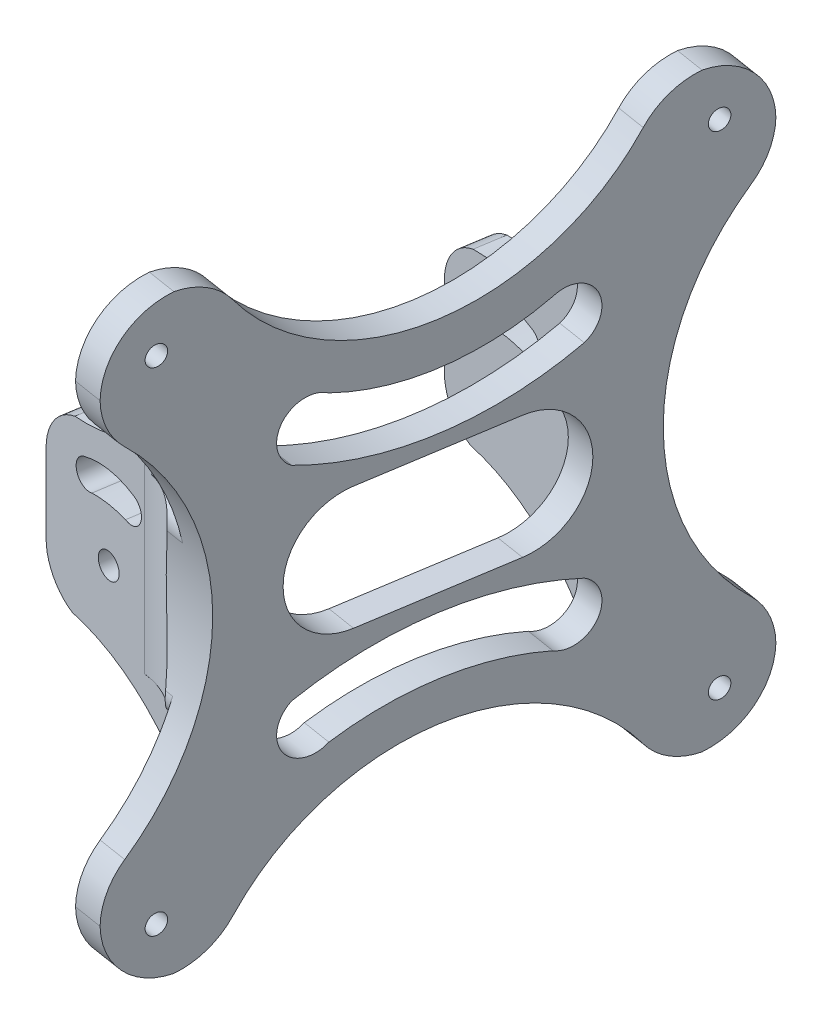
SolidWorks part; units mm, degrees
ref_plane "Plan de face" through (0, 0, 0) normal (0, 0, 1) x (1, 0, 0)
ref_plane "Plan de dessus" through (0, 0, 0) normal (0, 1, 0) x (1, 0, 0)
ref_plane "Plan de droite" through (0, 0, 0) normal (1, 0, 0) x (0, 0, -1)
sketch "Esquisse2" plane through (0.9062, 0, -5.7217) normal (-0.1564, 0, 0.9877) x (0.9877, 0, 0.1564)
  line L0 (50, 13.8449) -> (13, 13.8449)
  line L1 (13, 13.8449) -> (13, -22.1551)
  line L6 (13, -22.1551) -> (50, -22.1551)
  line L7 (50, 13.8449) -> (50, -22.1551)
  circle A0 centre (28.3, -8.1551) radius 2.55
  arc A9 (34.496, 7.5776) -> (32.4193, 2.2798) centre (33.4577, 4.9287) cw
  arc A11 (22.1493, 7.5776) -> (24.2261, 2.2798) centre (23.1877, 4.9287) ccw
  arc A12 (22.1493, 7.5776) -> (34.496, 7.5776) centre (28.3227, -8.1708) cw
  arc A14 (24.2261, 2.2798) -> (32.4193, 2.2798) centre (28.3227, -21.4961) cw
  dimension "D1" = 36
  dimension "D2" = 37
  dimension "D3" = 15.3
  dimension "D4" = 14
extrude "Boss.-Extru.1" add sketch "Esquisse2" along normal blind 6
sketch "Esquisse8" plane through (11.0275, 0, -69.6251) normal (0.1564, 0, -0.9877) x (-0.9877, 0, -0.1564)
  line L0 (-50, 13.8449) -> (-13, 13.8449)
  line L5 (-13, 13.8449) -> (-13, -22.1551)
  line L6 (-13, -22.1551) -> (-50, -22.1551)
  line L7 (-50, -22.1551) -> (-50, 13.8449)
  circle A0 centre (-28.3, -8.1551) radius 2.55
  arc A1 (-22.1493, 7.5776) -> (-24.2261, 2.2798) centre (-23.1877, 4.9287) cw
  arc A2 (-34.496, 7.5776) -> (-32.4193, 2.2798) centre (-33.4577, 4.9287) ccw
  arc A3 (-34.496, 7.5776) -> (-22.1493, 7.5776) centre (-28.3227, -8.1708) cw
  arc A5 (-32.4193, 2.2798) -> (-24.2261, 2.2798) centre (-28.3227, -20.7951) cw
  point P14 (-28.6739, -22.1551)
  dimension "D1" = 15.3
  dimension "D2" = 14
  dimension "D3" = 36
extrude "Boss.-Extru.3" add sketch "Esquisse8" along normal blind 6 separate body
sketch "Esquisse7" plane through (49.3844, 0, 7.8217) normal (0.9877, 0, 0.1564) x (0.1564, 0, -0.9877)
  line L6 (-21.8658, 59.4655) -> (98.1342, 59.4655)
  line L7 (-21.8658, 59.4655) -> (-21.8658, -60.5345)
  line L8 (-21.8658, -60.5345) -> (98.1342, -60.5345)
  line L9 (98.1342, 59.4655) -> (98.1342, -60.5345)
  circle A0 centre (-11.8658, 49.4655) radius 2
  circle A1 centre (88.1342, 49.4655) radius 2
  circle A2 centre (88.1342, -50.5345) radius 2
  circle A3 centre (-11.8658, -50.5345) radius 2
extrude "Boss.-Extru.5" add sketch "Esquisse7" along normal blind 6
sketch "Esquisse13" plane through (49.3844, 0, 7.8217) normal (-0.9877, 0, -0.1564) x (-0.1564, 0, 0.9877)
  line L0 (-98.1342, -60.5345) -> (-98.1342, 59.4655) construction
  line L1 (-76.493, 13.8449) -> (-98.1342, 13.8449)
  line L2 (-76.493, 13.8449) -> (-76.493, -22.048)
  line L3 (-76.493, -22.048) -> (-98.1342, -22.048)
  line L4 (-98.1342, 13.8449) -> (-98.1342, -22.048)
  line L5 (21.8658, 59.4655) -> (21.8658, -60.5345) construction
  line L6 (0.207, 13.8449) -> (21.8658, 13.8449)
  line L7 (0.207, 13.8449) -> (0.207, -22.2148)
  line L8 (0.207, -22.2148) -> (21.8658, -22.2148)
  line L9 (21.8658, 13.8449) -> (21.8658, -22.2148)
extrude "Boss.-Extru.6" add sketch "Esquisse13" along normal blind 13
sketch "Esquisse9" plane through (49.3844, 0, 7.8217) normal (-0.9877, 0, -0.1564) x (-0.1564, 0, 0.9877)
  line L0 (-98.1342, -60.5345) -> (-98.1342, -22.048) construction
  line L1 (-98.1342, 59.4655) -> (21.8658, 59.4655) construction
  line L2 (21.8658, -60.5345) -> (-98.1342, -60.5345) construction
  line L4 (21.8658, 59.4655) -> (21.8658, 13.8449) construction
  line L5 (-98.1342, 39.4655) -> (-98.1342, -40.5345)
  line L6 (-78.1342, -60.5345) -> (1.8658, -60.5345)
  line L7 (21.8658, 39.4655) -> (21.8658, -40.5345)
  line L8 (1.8658, 59.4655) -> (-78.1342, 59.4655)
  arc A0 (-98.1342, 39.4655) -> (-98.1342, -40.5345) centre (-128.1342, -0.5345) cw
  arc A1 (-78.1342, 59.4655) -> (1.8658, 59.4655) centre (-38.1342, 80.081) ccw
  arc A2 (21.8658, 39.4655) -> (21.8658, -40.5345) centre (51.8658, -0.5345) ccw
  arc A3 (1.8658, -60.5345) -> (-78.1342, -60.5345) centre (-38.1342, -81.15) ccw
  dimension "D3" = 50
  dimension "D6" = 45
  dimension "D9" = 50
  dimension "D12" = 45
  dimension "D1" = 20
  dimension "D2" = 20
  dimension "D4" = 20
  dimension "D5" = 20
  dimension "D7" = 20
  dimension "D8" = 20
  dimension "D10" = 20
  dimension "D11" = 20
extrude "Enlèv. mat.-Extru.1" cut sketch "Esquisse9" against normal blind 10 and the other way blind 13
sketch "Esquisse10" plane through (49.3844, 0, 7.8217) normal (-0.9877, 0, -0.1564) x (-0.1564, 0, 0.9877)
  line L0 (-53.1342, -0.5345) -> (-23.1342, -0.5345) construction
  line L1 (-53.1342, 11.9655) -> (-23.1342, 11.9655)
  line L2 (-53.1342, -13.0345) -> (-23.1342, -13.0345)
  line L3 (-98.1342, 59.4655) -> (-78.1342, 59.4655) construction
  line L5 (-98.1342, 39.4655) -> (-98.1342, 59.4655) construction
  line L6 (21.8658, 59.4655) -> (21.8658, 39.4655) construction
  arc A0 (-53.1342, 11.9655) -> (-53.1342, -13.0345) centre (-53.1342, -0.5345) ccw
  arc A1 (-23.1342, -13.0345) -> (-23.1342, 11.9655) centre (-23.1342, -0.5345) ccw
  point P2 (-38.1342, -0.5345)
  dimension "D4" = 12.5
  dimension "D1" = 60
  dimension "D2" = 45
  dimension "D3" = 45
extrude "Enlèv. mat.-Extru.2" cut sketch "Esquisse10" against normal blind 10
fillet "Congé1" radius 14 12 edges at (64.5704, 59.4655, -68.8812) (67.6991, 59.4655, -88.635) (67.6991, -40.5345, -88.635) (52.0556, 59.4655, 10.1339) (48.9269, 59.4655, 29.8876) (48.9269, -40.5345, 29.8876) (67.6991, -60.5345, -88.635) (52.0556, -60.5345, 10.1339) (48.9269, 39.4655, 29.8876) (67.6991, 39.4655, -88.635) (64.5704, -60.5345, -68.8812) (48.9269, -60.5345, 29.8876)
fillet "Congé2" radius 10 4 edges at (24.3368, 13.8449, -70.5545) (24.3368, -22.1551, -70.5545) (13.2769, -22.1551, -0.725) (13.2769, 13.8449, -0.725)
sketch "Esquisse16" plane through (49.3844, 0, 7.8217) normal (-0.9877, 0, -0.1564) x (-0.1564, 0, 0.9877)
  line L0 (0.207, -22.1551) -> (-5.793, -22.1551) construction
  line L1 (-70.493, -22.1551) -> (-76.493, -22.1551)
  line L2 (-70.493, -22.1551) -> (-70.493, -41.1551)
  line L3 (-70.493, -41.1551) -> (-76.493, -41.1551)
  line L4 (-76.493, -22.1551) -> (-76.493, -41.1551)
  line L5 (-70.493, 13.8449) -> (-76.493, 13.8449)
  line L6 (-70.493, 13.8449) -> (-70.493, 33.8449)
  line L7 (-70.493, 33.8449) -> (-76.493, 33.8449)
  line L8 (-76.493, 13.8449) -> (-76.493, 33.8449)
  line L9 (-5.793, 13.8449) -> (0.207, 13.8449)
  line L10 (-5.793, 13.8449) -> (-5.793, 33.8449)
  line L11 (-5.793, 33.8449) -> (0.207, 33.8449)
  line L12 (0.207, 13.8449) -> (0.207, 33.8449)
  line L13 (-5.793, -22.1551) -> (0.207, -22.1551)
  line L14 (-5.793, -22.1551) -> (-5.793, -42.1551)
  line L15 (-5.793, -42.1551) -> (0.207, -42.1551)
  line L16 (0.207, -22.1551) -> (0.207, -42.1551)
  line L17 (-76.493, -22.1551) -> (-70.493, -22.1551) construction
  point P20 (0, 0)
  dimension "D1" = 20
  dimension "D2" = 20
  dimension "D3" = 20
  dimension "D4" = 19
  dimension "D5" = 6
  dimension "D6" = 6
  dimension "D7" = 6
  dimension "D8" = 6
  dimension "D9" = 0
  dimension "D10" = 0
extrude "Boss.-Extru.7" add sketch "Esquisse16" along normal blind 37
sketch "Esquisse17" plane through (-0.0324, 0, 0.2045) normal (-0.1564, 0, 0.9877) x (0.9877, 0, 0.1564)
  line L0 (50, 33.8449) -> (13, 33.8449)
  line L1 (13, 33.8449) -> (13, 13.5011)
  line L4 (13, -42.1551) -> (50, -42.1551) construction
  line L5 (50, -42.1551) -> (50, -22.2148) construction
  line L6 (13, -42.1551) -> (13, -21.5483)
  line L7 (13, -42.1551) -> (50, -42.1551)
  line L8 (13, 3.8449) -> (13, -12.1551) construction
  arc A2 (13, -21.5483) -> (50, -42.1551) centre (16.5937, -58.6163) cw
  arc A3 (13, 13.5011) -> (50, 33.8449) centre (17.0381, 49.9753) ccw
  point P4 (13, -21.5483)
  point P14 (13, 13.5011)
extrude "Enlèv. mat.-Extru.5" cut sketch "Esquisse17" against normal blind 102
sketch "Esquisse11" plane through (49.3844, 0, 7.8217) normal (-0.9877, 0, -0.1564) x (-0.1564, 0, 0.9877)
  circle A0 centre (-88.1342, 49.4655) radius 3.6
  circle A1 centre (11.8658, 49.4655) radius 3.6
  circle A2 centre (11.8658, -50.5345) radius 3.6
  circle A3 centre (-88.1342, -50.5345) radius 3.6
  dimension "D1" = 7.2
  dimension "D2" = 7.2
  dimension "D3" = 7.2
  dimension "D4" = 7.2
extrude "Enlèv. mat.-Extru.3" cut sketch "Esquisse11" against normal blind 2
fillet "Congé3" radius 4 4 edges at (42.3421, 13.8449, 10.734) (41.899, -22.2148, 13.5317) (55.5178, 13.8449, -72.4536) (55.9484, -22.048, -75.1724)
sketch "Esquisse18" plane through (49.3844, 0, 7.8217) normal (-0.9877, 0, -0.1564) x (-0.1564, 0, 0.9877)
  arc A4 (-58.5309, 30.6356) -> (-18.758, 30.1817) centre (-38.0971, 78.369) ccw
  arc A5 (-64.1065, 20.1757) -> (-12.1795, 20.1757) centre (-38.143, 81.8699) ccw
  arc A6 (-58.5309, -31.7046) -> (-18.758, -31.2507) centre (-37.9749, -90.1471) cw
  arc A7 (-64.1065, -21.2447) -> (-12.1795, -21.2447) centre (-38.143, -90.1935) cw
  arc A8 (-58.5309, 30.6356) -> (-64.1065, 20.1757) centre (-61.3187, 25.4057) ccw
  arc A9 (-18.758, 30.1817) -> (-12.1795, 20.1757) centre (-15.4687, 25.1787) cw
  arc A10 (-64.1065, -21.2447) -> (-58.5309, -31.7046) centre (-61.3187, -26.4746) ccw
  arc A11 (-12.1795, -21.2447) -> (-18.758, -31.2507) centre (-15.4687, -26.2477) cw
extrude "Enlèv. mat.-Extru.6" cut sketch "Esquisse18" against normal blind 10
sketch "Esquisse19" plane through (0, -22.2148, 0) normal (0, -1, 0) x (1, 0, 0)
  line L5 (48.319, 14.5486) -> (35.479, 12.5149)
  line L8 (48.5106, -69.7632) -> (49.5284, -76.1893)
  line L9 (49.5284, -76.1893) -> (62.3684, -74.1556)
  line L10 (48.5106, -69.7632) -> (61.3506, -67.7295) construction
  line L11 (35.479, 12.5149) -> (36.5121, 5.9925)
  arc A4 (48.5106, -69.7632) -> (62.3684, -74.1556) centre (51.4636, -84.503) cw
  arc A5 (36.5121, 5.9925) -> (48.319, 14.5486) centre (35.1402, 20.3102) ccw
  dimension "D1" = 0
  dimension "D2" = 0
  dimension "D3" = 0
  dimension "D4" = 0
extrude "Enlèv. mat.-Extru.7" cut sketch "Esquisse19" against normal blind 60
